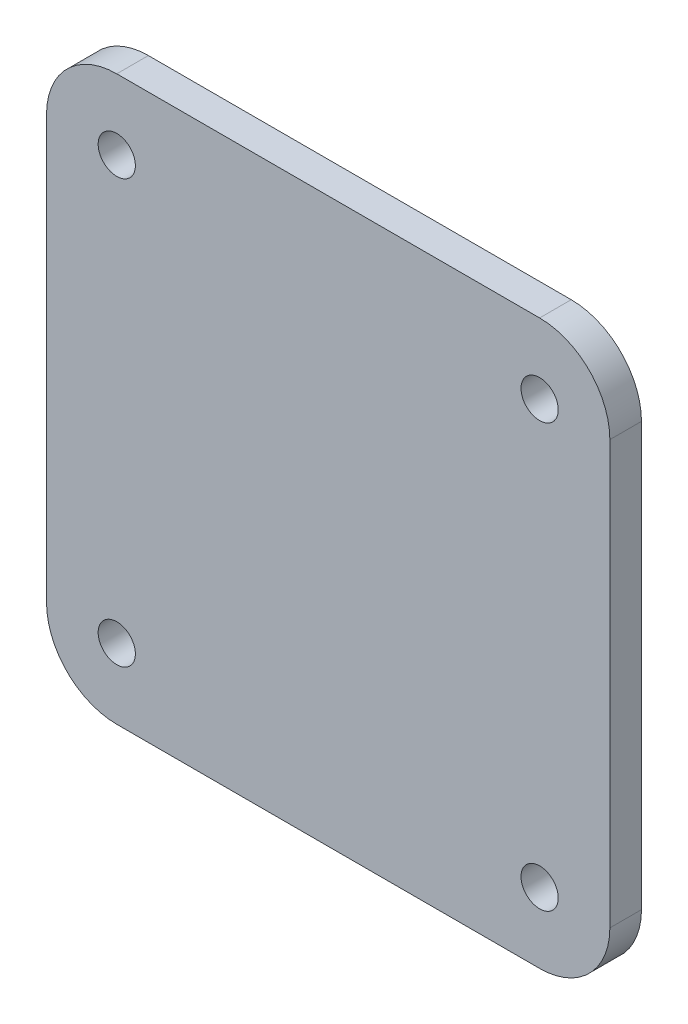
SolidWorks part; units mm, degrees
ref_plane "Front Plane" through (0, 0, 0) normal (0, 0, 1) x (1, 0, 0)
ref_plane "Top Plane" through (0, 0, 0) normal (0, 1, 0) x (1, 0, 0)
ref_plane "Right Plane" through (0, 0, 0) normal (1, 0, 0) x (0, 0, -1)
sketch "Sketch1" plane through (0, 0, 0) normal (0, 0, 1) x (1, 0, 0)
  line L0 (-30.1, 0) -> (30.1, 0) construction
  line L1 (-40.1, -40.1) -> (40.1, -40.1)
  line L2 (-40.1, -40.1) -> (-40.1, 40.1)
  line L3 (-40.1, 40.1) -> (40.1, 40.1)
  line L4 (40.1, -40.1) -> (40.1, 40.1)
  line L5 (-40.1, -40.1) -> (40.1, 40.1) construction
  line L6 (-40.1, 40.1) -> (40.1, -40.1) construction
  line L7 (55, 0) -> (-55, 0) construction
  line L8 (-30.1, -30.1) -> (-30.1, 30.1) construction
  line L9 (30.1, -30.1) -> (30.1, 30.1) construction
  point P0 (0, 0)
  point P11 (0, 0)
  point P14 (-30.1, 0)
  point P17 (30.1, 0)
  dimension "D1" = 60.2
  dimension "D2" = 10
  dimension "D3" = 10
extrude "Boss-Extrude1" add sketch "Sketch1" along normal blind 4.5 contours L2 L3 L4 L1
hole_wizard "M5 Clearance Hole1" positions "3DSketch1" profile "Sketch2" hole size "M5" standard "ANSI Metric" end condition through all
sketch3d "3DSketch1"
  point P0 (30.1, 30.1, 0)
  point P2 (-30.1, 30.1, 0)
  point P4 (-30.1, -30.1, 0)
  point P6 (30.1, -30.1, 0)
sketch "Sketch2" plane through (30.1, 30.1, 0) normal (1, 0, 0) x (0, 1, 0)
  line L0 (0, 0) -> (0, 4.5)
  line L1 (0, 4.5) -> (2.65, 4.5)
  line L2 (2.65, 4.5) -> (2.65, 0)
  line L5 (2.65, 0) -> (0, 0)
  line L11 (0, -6.35) -> (0, 107.95) construction
  dimension "Thru Hole Dia." = 5.3
  dimension "Thru Hole Depth" = 4.5
fillet "Fillet1" radius 10 4 edges at (-40.1, 40.1, 2.25) (-40.1, -40.1, 2.25) (40.1, -40.1, 2.25) (40.1, 40.1, 2.25)
